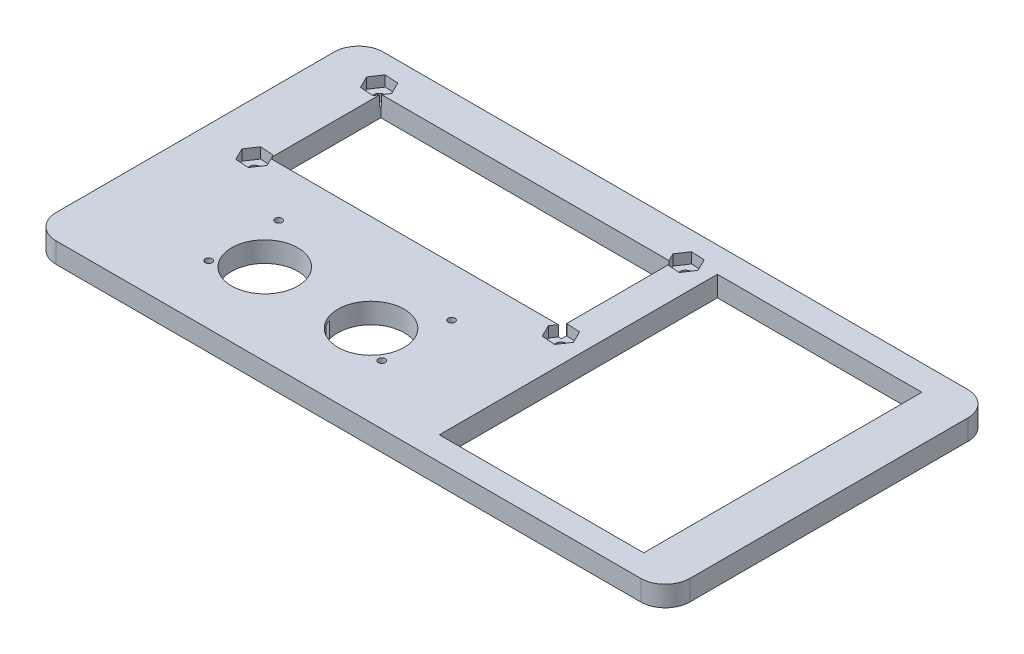
SolidWorks part; units mm, degrees
ref_plane "Front Plane" through (0, 0, 0) normal (0, 0, 1) x (1, 0, 0)
ref_plane "Top Plane" through (0, 0, 0) normal (0, 1, 0) x (1, 0, 0)
ref_plane "Right Plane" through (0, 0, 0) normal (1, 0, 0) x (0, 0, -1)
sketch "Sketch1" plane through (0, 0, 0) normal (0, 1, 0) x (1, 0, 0)
  line L1 (-77.5, -40) -> (77.5, -40)
  line L2 (-77.5, -40) -> (-77.5, 40)
  line L3 (-77.5, 40) -> (77.5, 40)
  line L4 (77.5, -40) -> (77.5, 40)
  line L5 (-77.5, -40) -> (77.5, 40) construction
  line L6 (-77.5, 40) -> (77.5, -40) construction
  point P0 (0, 0)
  dimension "D1" = 155
  dimension "D2" = 80
extrude "Boss-Extrude1" add sketch "Sketch1" along normal blind 5
sketch "Sketch2" plane through (0, 5, 0) normal (0, 1, 0) x (1, 0, 0)
  line L1 (-62.8518, 3.6691) -> (8.446, 3.6691)
  line L2 (-62.8518, 3.6691) -> (-62.8518, 30.7709)
  line L3 (-62.8518, 30.7709) -> (8.446, 30.7709)
  line L4 (8.446, 3.6691) -> (8.446, 30.7709)
  line L5 (-62.8518, 3.6691) -> (8.446, 30.7709) construction
  line L6 (-62.8518, 30.7709) -> (8.446, 3.6691) construction
  line L7 (-67.5, 17.22) -> (12.51, 17.22) construction
  line L8 (-67.5, 35) -> (12.51, 35) construction
  line L9 (-67.5, 35) -> (-67.5, -0.56) construction
  line L10 (-67.5, -0.56) -> (12.51, -0.56) construction
  line L11 (12.51, 35) -> (12.51, -0.56) construction
  line L12 (77.5, 40) -> (-77.5, 40) construction
  line L13 (-77.5, 40) -> (-77.5, -40) construction
  circle A0 centre (-64.96, 1.98) radius 1.27
  circle A1 centre (9.97, 1.98) radius 1.27
  circle A2 centre (9.97, 32.46) radius 1.27
  circle A3 centre (-64.96, 32.46) radius 1.27
  point P0 (-27.2029, 17.22)
  point P7 (0, 0)
  point P8 (0, 0)
  point P20 (-27.495, 17.22)
  point P23 (0, 0)
  point P24 (-51.7827, 14.22)
  dimension "D7" = 2.54
  dimension "D8" = 2.54
  dimension "D1" = 71.2978
  dimension "D2" = 27.1018
  dimension "D3" = 5
  dimension "D4" = 35.56
  dimension "D5" = 80.01
  dimension "D6" = 4.6482
  dimension "D9" = 33.02
  dimension "D10" = 77.47
  dimension "D11" = 5.08
  dimension "D12" = 10
extrude "Screen Cutout" cut sketch "Sketch2" against normal through all
sketch "Sketch8" plane through (0, 5, 0) normal (0, 1, 0) x (1, 0, 0)
  line L1 (-66.7896, 29.7246) -> (-63.5059, 29.5078)
  line L2 (-63.5059, 29.5078) -> (-61.6763, 32.2432)
  line L3 (-61.6763, 32.2432) -> (-63.1304, 35.1954)
  line L4 (-63.1304, 35.1954) -> (-66.4141, 35.4122)
  line L5 (-66.4141, 35.4122) -> (-68.2437, 32.6768)
  line L6 (-68.2437, 32.6768) -> (-66.7896, 29.7246)
  line L7 (8.1404, 29.7246) -> (11.4241, 29.5078)
  line L8 (11.4241, 29.5078) -> (13.2537, 32.2432)
  line L9 (13.2537, 32.2432) -> (11.7996, 35.1954)
  line L10 (11.7996, 35.1954) -> (8.5159, 35.4122)
  line L11 (8.5159, 35.4122) -> (6.6863, 32.6768)
  line L12 (6.6863, 32.6768) -> (8.1404, 29.7246)
  line L13 (8.1404, -0.7554) -> (11.4241, -0.9722)
  line L14 (11.4241, -0.9722) -> (13.2537, 1.7632)
  line L15 (13.2537, 1.7632) -> (11.7996, 4.7154)
  line L16 (11.7996, 4.7154) -> (8.5159, 4.9322)
  line L17 (8.5159, 4.9322) -> (6.6863, 2.1968)
  line L18 (6.6863, 2.1968) -> (8.1404, -0.7554)
  line L19 (-66.7896, -0.7554) -> (-63.5059, -0.9722)
  line L20 (-63.5059, -0.9722) -> (-61.6763, 1.7632)
  line L21 (-61.6763, 1.7632) -> (-63.1304, 4.7154)
  line L22 (-63.1304, 4.7154) -> (-66.4141, 4.9322)
  line L23 (-66.4141, 4.9322) -> (-68.2437, 2.1968)
  line L24 (-68.2437, 2.1968) -> (-66.7896, -0.7554)
  circle A0 centre (-64.96, 32.46) radius 2.85 construction
  circle A1 centre (9.97, 32.46) radius 2.85 construction
  circle A2 centre (9.97, 1.98) radius 2.85 construction
  circle A3 centre (-64.96, 1.98) radius 2.85 construction
  dimension "D1" = 5.7
extrude "Screen hex nuts" cut sketch "Sketch8" against normal blind 2.6
sketch "Sketch3" plane through (0, 5, 0) normal (0, 1, 0) x (1, 0, 0)
  line L0 (-40.472, -20) -> (-14.472, -20) construction
  line L1 (-48.622, -8.45) -> (-48.622, -25.55) construction
  line L2 (-48.622, -25.55) -> (-6.322, -25.55) construction
  line L3 (-62.615, 3.6691) -> (7.671, 3.6691) construction
  line L4 (-77.5, -40) -> (77.5, -40) construction
  line L7 (-27.472, 26.9252) -> (-27.472, -22.8987) construction
  circle A0 centre (-40.472, -20) radius 8.1
  circle A1 centre (-14.472, -20) radius 8.1
  circle A2 centre (-48.622, -8.45) radius 0.85
  circle A3 centre (-6.322, -8.45) radius 0.85
  circle A4 centre (-6.322, -25.55) radius 0.85
  circle A5 centre (-48.622, -25.55) radius 0.85
  point P4 (-27.472, -25.55)
  point P14 (-27.472, -20)
  point P19 (-27.472, 3.6691)
  dimension "D1" = 16.2
  dimension "D2" = 26
  dimension "D3" = 1.7
  dimension "D4" = 17.1
  dimension "D5" = 20
  dimension "D6" = 42.3
extrude "Ultrasound Cutouts" cut sketch "Sketch3" against normal through all
sketch "Sketch4" plane through (0, 5, 0) normal (0, 1, 0) x (1, 0, 0)
  circle A0 centre (-21.6513, -28.8183) radius 0.85
  circle A1 centre (20.3487, -11.8183) radius 0.85
  circle A2 centre (-21.6513, -11.8183) radius 0.85
  circle A3 centre (20.3487, -28.8183) radius 0.85
  dimension "D1" = 1.7
  dimension "D2" = 17
  dimension "D3" = 42
extrude "Ultrasound Bolt Holes" [suppressed] cut sketch "Sketch4" against normal through all
sketch "Sketch5" plane through (0, 0, 0) normal (0, -1, 0) x (1, 0, 0)
  line L0 (-6.322, 26.4) -> (-48.622, 26.4) construction
  line L1 (-21.472, 26.4) -> (-33.472, 26.4)
  line L2 (-21.472, 26.4) -> (-21.472, 22.4)
  line L3 (-21.472, 22.4) -> (-33.472, 22.4)
  line L4 (-33.472, 26.4) -> (-33.472, 22.4)
  line L5 (-21.472, 26.4) -> (-33.472, 22.4) construction
  line L6 (-21.472, 22.4) -> (-33.472, 26.4) construction
  circle A3 centre (-6.322, 25.55) radius 0.85 construction
  circle A4 centre (-48.622, 25.55) radius 0.85 construction
  point P0 (-27.472, 24.4)
  point P11 (48.0699, 24.4)
  point P12 (49.1908, 24.4)
  point P13 (-27.472, 26.4)
  point P14 (-27.472, 26.4)
  point P15 (-72.9327, 26.4)
  dimension "D1" = 12
  dimension "D2" = 4
extrude "US Clock cutout" cut sketch "Sketch5" against normal blind 4
sketch "Sketch6" plane through (0, 0, 0) normal (0, -1, 0) x (1, 0, 0)
  line L0 (-21.472, 25.2378) -> (-33.472, 25.2378) construction
  line L1 (-22.472, 10.9878) -> (-32.472, 10.9878)
  line L2 (-22.472, 10.9878) -> (-22.472, 7.4878)
  line L3 (-22.472, 7.4878) -> (-32.472, 7.4878)
  line L4 (-32.472, 10.9878) -> (-32.472, 7.4878)
  line L5 (-22.472, 10.9878) -> (-32.472, 7.4878) construction
  line L6 (-22.472, 7.4878) -> (-32.472, 10.9878) construction
  line L7 (-21.472, 24.0755) -> (-21.472, 26.4) construction
  line L8 (-33.472, 26.4) -> (-33.472, 24.0755) construction
  line L9 (-7.172, 8.45) -> (-49.472, 8.45) construction
  line L10 (-27.472, 5.8213) -> (-27.472, 1.0358) construction
  circle A0 centre (-6.322, 8.45) radius 0.85 construction
  circle A1 centre (-48.622, 8.45) radius 0.85 construction
  point P0 (-27.472, 9.2378)
  point P19 (0, 8.4)
  point P20 (-27.472, 25.2378)
  dimension "D1" = 10
  dimension "D2" = 3.5
  dimension "D3" = 16
extrude "US Pin cutout" cut sketch "Sketch6" against normal blind 2
fillet "Fillet2" [suppressed] radius 1
ref_plane "Magnet plane" through (0, 0.2, 0) normal (0, -1, 0) x (-1, 0, 0)
sketch "Sketch9" plane through (0, 0.2, 0) normal (0, -1, 0) x (-1, 0, 0)
  line L0 (-77.5, -40) -> (-77.5, 40) construction
  line L1 (-77.5, 40) -> (77.5, 40) construction
  line L2 (77.5, -40) -> (-77.5, -40) construction
  line L3 (77.5, 40) -> (77.5, -40) construction
  circle A0 centre (-71.5, 34) radius 3.15
  circle A1 centre (71.5, 34) radius 3.15
  circle A2 centre (-71.5, -34) radius 3.15
  circle A3 centre (71.5, -34) radius 3.15
  point P8 (0, 0)
  point P9 (0, 0)
  point P10 (0, 0)
  point P11 (0, 0)
  dimension "D1" = 6.3
  dimension "D2" = 6
  dimension "D3" = 6
  dimension "D4" = 6
  dimension "D5" = 6
extrude "Magnet Holes" cut sketch "Sketch9" against normal blind 2.1
fillet "Fillet1" radius 6 4 edges at (77.5, 2.5, -40) (77.5, 2.5, 40) (-77.5, 2.5, 40) (-77.5, 2.5, -40)
sketch "Sketch10" plane through (0, 5, 0) normal (0, 1, 0) x (1, 0, 0)
  line L0 (8.446, 4.8277) -> (8.446, 29.7044) construction
  line L1 (16.446, -34.2171) -> (66.446, -34.2171)
  line L2 (16.446, -34.2171) -> (16.446, 33.7829)
  line L3 (16.446, 33.7829) -> (66.446, 33.7829)
  line L4 (66.446, -34.2171) -> (66.446, 33.7829)
  line L5 (16.446, -34.2171) -> (66.446, 33.7829) construction
  line L6 (16.446, 33.7829) -> (66.446, -34.2171) construction
  point P0 (41.446, -0.2171)
  dimension "D1" = 50
  dimension "D2" = 68
  dimension "D3" = 8
extrude "Keypad cutout" cut sketch "Sketch10" against normal through all
